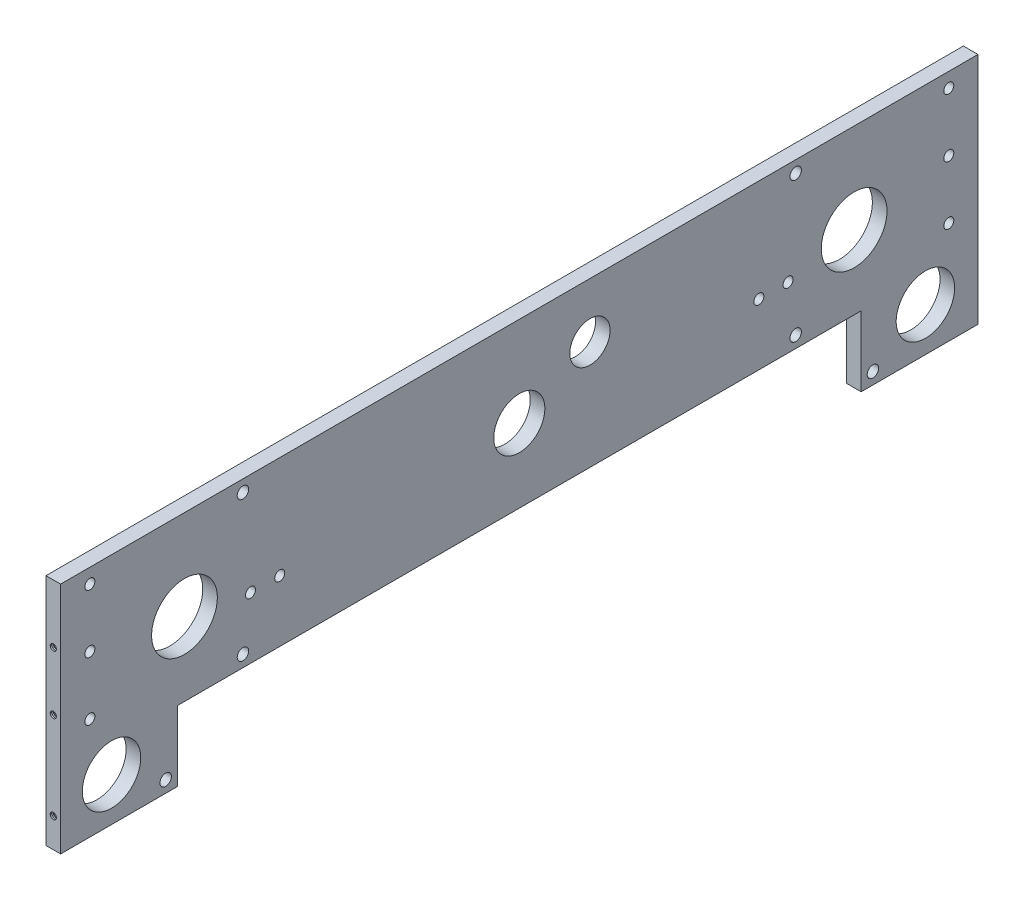
SolidWorks part; units mm, degrees
material "6061-T6 (SS)"
ref_plane "Front Plane" through (0, 0, 0) normal (0, 0, 1) x (1, 0, 0)
ref_plane "Top Plane" through (0, 0, 0) normal (0, 1, 0) x (1, 0, 0)
ref_plane "Right Plane" through (0, 0, 0) normal (1, 0, 0) x (0, 0, -1)
sketch "Sketch1" plane through (0, 0, 0) normal (1, 0, 0) x (0, 0, -1)
  line L1 (-199.39, 50.8) -> (199.39, 50.8)
  line L2 (-199.39, 50.8) -> (-199.39, -50.8)
  line L3 (-199.39, -50.8) -> (199.39, -50.8)
  line L4 (199.39, 50.8) -> (199.39, -50.8)
  line L5 (-199.39, 50.8) -> (199.39, -50.8) construction
  line L6 (-199.39, -50.8) -> (199.39, 50.8) construction
  point P0 (0, 0)
  dimension "D1" = 101.6
  dimension "D2" = 398.78
extrude "Boss-Extrude1" add sketch "Sketch1" along normal blind 6.35
sketch "Sketch2" plane through (6.35, 0, 0) normal (1, 0, 0) x (0, 0, -1)
  line L0 (-199.39, -50.8) -> (199.39, -50.8) construction
  line L1 (-145.5447, 11.6882) -> (0, 11.6882) construction
  line L2 (199.39, 50.8) -> (-199.39, 50.8) construction
  line L3 (0, 11.6882) -> (145.5447, 11.6882) construction
  line L4 (1.4287, 28.7746) -> (-143.1055, 40.86) construction
  line L5 (1.4287, -5.3983) -> (-143.1055, -17.4837) construction
  line L10 (0.9292, 22.8011) -> (-143.605, 34.8865) construction
  line L11 (-199.39, 50.8) -> (-199.39, -50.8) construction
  line L12 (-148.59, -50.8) -> (0, -50.8)
  line L13 (-148.59, -50.8) -> (-148.59, -20.32)
  line L14 (-148.59, -20.32) -> (148.59, -20.32)
  line L15 (0, -50.8) -> (0, -20.32) construction
  line L16 (199.39, -50.8) -> (199.39, 50.8) construction
  line L17 (-163.0212, -41.4951) -> (-132.9859, 3.2599) construction
  line L18 (0.9292, 0.5753) -> (-143.605, -11.5102) construction
  line L19 (-177.2583, -31.9405) -> (-199.39, -31.9405) construction
  line L20 (-177.2583, -31.9405) -> (-158.1418, -43.0925) construction
  line L21 (148.59, -50.8) -> (148.59, -20.32)
  line L22 (0, -50.8) -> (148.59, -50.8)
  line L23 (-120.1014, -15.5602) -> (-120.5589, -10.0878) construction
  line L24 (-120.5589, 40.5678) -> (-120.6912, 38.9858) construction
  circle A1 centre (-145.5447, 11.6882) radius 14.2875
  circle A2 centre (145.5447, 11.6882) radius 14.2875
  circle A3 centre (-145.5447, 11.6882) radius 29.2737 construction
  circle A4 centre (0, 11.6882) radius 30.48 construction
  circle A5 centre (145.5447, 11.6882) radius 29.2737 construction
  circle A11 centre (-177.2583, -31.9405) radius 12.7
  circle A12 centre (176.53, -31.9405) radius 12.7
  circle A13 centre (0, 11.6882) radius 11.1125
  circle A14 centre (-177.2583, -31.9405) radius 20.6375 construction
  circle A15 centre (-177.2583, -31.9405) radius 17.1461 construction
  circle A16 centre (-145.5447, 11.6882) radius 15.1248 construction
  circle A17 centre (0, 11.6882) radius 17.1461 construction
  circle A18 centre (34.3662, 11.6882) radius 8.7754 construction
  circle A19 centre (-153.715, -45.675) radius 5.125 construction
  circle A20 centre (-153.715, -45.675) radius 2.4892
  circle A21 centre (-120.1319, 45.675) radius 5.125 construction
  circle A22 centre (-120.1319, -15.195) radius 5.125 construction
  circle A23 centre (-120.1319, -15.195) radius 2.4892
  circle A24 centre (-120.1319, 45.675) radius 2.4892
  circle A25 centre (120.1319, 45.675) radius 2.4892
  circle A26 centre (120.1319, -15.195) radius 2.4892
  circle A27 centre (153.715, -45.675) radius 2.4892
  circle A28 centre (0, 11.6882) radius 29.21 construction
  circle A29 centre (30.7172, 26.9282) radius 5.08 construction
  circle A30 centre (30.7172, 26.9282) radius 8.75
  point P11 (0, 0)
  point P12 (0, -18.7918)
  point P14 (0, 42.1682)
  point P52 (-197.8958, -31.9405)
  point P56 (-159.8322, 11.6882)
  dimension "D1" = 28.575
  dimension "D5" = 58.5474
  dimension "D7" = 8.6318
  dimension "D14" = 25.4
  dimension "D15" = 53.9371
  dimension "D17" = 25.4
  dimension "D20" = 22.225
  dimension "D21" = 28.575
  dimension "D22" = 60.96
  dimension "D23" = 41.275
  dimension "D27" = 34.2921
  dimension "D28" = 30.2496
  dimension "D12" = 17.5508
  dimension "D13" = 10.25
  dimension "D29" = 4.9784
  dimension "D26" = 1.5875
  dimension "D30" = 4.9784
  dimension "D31" = 58.42
  dimension "D32" = 10.16
  dimension "D33" = 17.5001
  dimension "D3" = 39.5578
  dimension "D4" = 145.5447
  dimension "D6" = 0
  dimension "D8" = 1.5282
  dimension "D9" = 5.9944
  dimension "D10" = 5.9944
  dimension "D11" = 34.3662
  dimension "D16" = 1.4942
  dimension "D18" = 18.8595
  dimension "D19" = 22.86
  dimension "D24" = 30.48
  dimension "D25" = 50.8
  dimension "D34" = 15.24
extrude "Cut-Extrude1" cut sketch "Sketch2" against normal through all
sketch "Sketch3" plane through (6.35, 0, 0) normal (1, 0, 0) x (0, 0, -1)
  line L0 (-193.294, 19.05) -> (-193.294, -19.05) construction
  line L1 (-199.39, 50.8) -> (-199.39, -50.8) construction
  point P2 (-193.294, 0)
  point P3 (-199.39, 0)
  dimension "D1" = 38.1
  dimension "D2" = 6.096
sketch "Sketch27" plane through (0, 0, -199.39) normal (0, 0, -1) x (-1, 0, 0)
  line L0 (-6.35, 50.8) -> (0, 50.8) construction
  line L1 (-6.35, -50.8) -> (-6.35, 50.8) construction
  point P0 (-3.175, 25.4)
  point P1 (-3.175, 0)
  point P2 (-3.175, -38.1)
  dimension "D1" = 25.4
  dimension "D2" = 3.175
hole_wizard "#36 (0.1065) Diameter Hole2" positions "Sketch28" profile "Sketch29" hole size "#36" standard "ANSI Inch"
sketch "Sketch28" plane through (0, 0, -199.39) normal (0, 0, -1) x (-1, 0, 0)
  point P0 (-3.175, 25.4)
  point P3 (-3.175, 0)
  point P6 (-3.175, -38.1)
sketch "Sketch29" plane through (3.175, 25.4, -199.39) normal (1, 0, 0) x (0, 1, 0)
  line L0 (0, 0) -> (0, 9.7027)
  line L1 (0, 9.7027) -> (1.3525, 8.89)
  line L2 (1.3525, 8.89) -> (1.3525, 0)
  line L5 (1.3525, 0) -> (0, 0)
  line L10 (0, 9.7027) -> (-1.3526, 8.89) construction
  line L11 (0, -6.35) -> (0, 107.95) construction
  dimension "Hole Dia." = 2.7051
  dimension "Hole Depth" = 8.89
  dimension "Drill Angle" = 118
thread "Thread3" pitch 0.7937 method cut profile "Thread Profile3" start angle 0, offset 0, length 6.35, pitch 0.7937, diameter 2.7051
ref_plane "Plane3" through (4.5275, 25.4, -199.39) normal (0, -1, 0) x (1, 0, 0)
sketch "Thread Profile3" plane through (4.5275, 25.4, -199.39) normal (0, -1, 0) x (1, 0, 0)
  line L0 (0, 0) -> (0, 0.7937) construction
  line L1 (0, 0) -> (0.4296, 0.248)
  line L2 (0.4296, 0.248) -> (0.4296, 0.3473)
  line L3 (0.4296, 0.3473) -> (0, 0.5953)
  line L4 (0.4296, 0.2977) -> (0, 0.2977) construction
  line L11 (0, 0) -> (0, 0.5953)
  point P2 (0, 0)
  dimension "Pitch" = 0.7937
  dimension "Profile_Angle" = 60
  dimension "Profile_Land" = 0.0992
  dimension "Profile_Height" = 0.4296
thread "Thread4" pitch 0.7937 method cut profile "Thread Profile4" start angle 0, offset 0, length 6.35, pitch 0.7937, diameter 2.7051
ref_plane "Plane4" through (4.5275, 0, -199.39) normal (0, -1, 0) x (1, 0, 0)
sketch "Thread Profile4" plane through (4.5275, 0, -199.39) normal (0, -1, 0) x (1, 0, 0)
  line L0 (0, 0) -> (0, 0.7937) construction
  line L1 (0, 0) -> (0.4296, 0.248)
  line L2 (0.4296, 0.248) -> (0.4296, 0.3473)
  line L3 (0.4296, 0.3473) -> (0, 0.5953)
  line L4 (0.4296, 0.2977) -> (0, 0.2977) construction
  line L11 (0, 0) -> (0, 0.5953)
  point P2 (0, 0)
  dimension "Pitch" = 0.7937
  dimension "Profile_Angle" = 60
  dimension "Profile_Land" = 0.0992
  dimension "Profile_Height" = 0.4296
thread "Thread5" pitch 0.7937 method cut profile "Thread Profile5" start angle 0, offset 0, length 6.35, pitch 0.7937, diameter 2.7051
ref_plane "Plane5" through (4.5275, -38.1, -199.39) normal (0, -1, 0) x (1, 0, 0)
sketch "Thread Profile5" plane through (4.5275, -38.1, -199.39) normal (0, -1, 0) x (1, 0, 0)
  line L0 (0, 0) -> (0, 0.7937) construction
  line L1 (0, 0) -> (0.4296, 0.248)
  line L2 (0.4296, 0.248) -> (0.4296, 0.3473)
  line L3 (0.4296, 0.3473) -> (0, 0.5953)
  line L4 (0.4296, 0.2977) -> (0, 0.2977) construction
  line L11 (0, 0) -> (0, 0.5953)
  point P2 (0, 0)
  dimension "Pitch" = 0.7937
  dimension "Profile_Angle" = 60
  dimension "Profile_Land" = 0.0992
  dimension "Profile_Height" = 0.4296
sketch "Sketch36" plane through (0, 0, 199.39) normal (0, 0, 1) x (1, 0, 0)
  line L0 (6.35, 50.8) -> (6.35, -50.8) construction
  line L1 (6.35, 50.8) -> (0, 50.8) construction
  point P0 (3.175, 25.4)
  point P1 (3.175, -12.7)
  point P2 (3.175, -50.8)
  dimension "D1" = 25.4
  dimension "D2" = 3.175
  dimension "D3" = 38.1
  dimension "D4" = 38.1
hole_wizard "#36 (0.1065) Diameter Hole3" positions "Sketch37" profile "Sketch38" hole size "#36" standard "ANSI Inch"
sketch "Sketch37" plane through (0, 0, 199.39) normal (0, 0, 1) x (1, 0, 0)
  point P0 (3.175, 25.4)
  point P3 (3.175, 0)
  point P6 (3.175, -38.1)
sketch "Sketch38" plane through (3.175, 25.4, 199.39) normal (1, 0, 0) x (0, -1, 0)
  line L0 (0, 0) -> (0, 9.7027)
  line L1 (0, 9.7027) -> (1.3525, 8.89)
  line L2 (1.3525, 8.89) -> (1.3525, 0)
  line L5 (1.3525, 0) -> (0, 0)
  line L10 (0, 9.7027) -> (-1.3525, 8.89) construction
  line L11 (0, -6.35) -> (0, 107.95) construction
  dimension "Hole Dia." = 2.7051
  dimension "Hole Depth" = 8.89
  dimension "Drill Angle" = 118
thread "Thread6" pitch 0.7937 method cut profile "Thread Profile6" start angle 0, offset 0, length 6.35, pitch 0.7937, diameter 2.7051
ref_plane "Plane6" through (1.8225, 25.4, 199.39) normal (0, -1, 0) x (-1, 0, 0)
sketch "Thread Profile6" plane through (1.8225, 25.4, 199.39) normal (0, -1, 0) x (-1, 0, 0)
  line L0 (0, 0) -> (0, 0.7937) construction
  line L1 (0, 0) -> (0.4296, 0.248)
  line L2 (0.4296, 0.248) -> (0.4296, 0.3473)
  line L3 (0.4296, 0.3473) -> (0, 0.5953)
  line L4 (0.4296, 0.2977) -> (0, 0.2977) construction
  line L11 (0, 0) -> (0, 0.5953)
  point P2 (0, 0)
  dimension "Pitch" = 0.7937
  dimension "Profile_Angle" = 60
  dimension "Profile_Land" = 0.0992
  dimension "Profile_Height" = 0.4296
thread "Thread7" pitch 0.7937 method cut profile "Thread Profile7" start angle 0, offset 0, length 6.35, pitch 0.7937, diameter 2.7051
ref_plane "Plane7" through (1.8225, 0, 199.39) normal (0, -1, 0) x (-1, 0, 0)
sketch "Thread Profile7" plane through (1.8225, 0, 199.39) normal (0, -1, 0) x (-1, 0, 0)
  line L0 (0, 0) -> (0, 0.7937) construction
  line L1 (0, 0) -> (0.4296, 0.248)
  line L2 (0.4296, 0.248) -> (0.4296, 0.3473)
  line L3 (0.4296, 0.3473) -> (0, 0.5953)
  line L4 (0.4296, 0.2977) -> (0, 0.2977) construction
  line L11 (0, 0) -> (0, 0.5953)
  point P2 (0, 0)
  dimension "Pitch" = 0.7937
  dimension "Profile_Angle" = 60
  dimension "Profile_Land" = 0.0992
  dimension "Profile_Height" = 0.4296
thread "Thread8" pitch 0.7937 method cut profile "Thread Profile8" start angle 0, offset 0, length 6.35, pitch 0.7937, diameter 2.7051
ref_plane "Plane8" through (1.8225, -38.1, 199.39) normal (0, -1, 0) x (-1, 0, 0)
sketch "Thread Profile8" plane through (1.8225, -38.1, 199.39) normal (0, -1, 0) x (-1, 0, 0)
  line L0 (0, 0) -> (0, 0.7937) construction
  line L1 (0, 0) -> (0.4296, 0.248)
  line L2 (0.4296, 0.248) -> (0.4296, 0.3473)
  line L3 (0.4296, 0.3473) -> (0, 0.5953)
  line L4 (0.4296, 0.2977) -> (0, 0.2977) construction
  line L11 (0, 0) -> (0, 0.5953)
  point P2 (0, 0)
  dimension "Pitch" = 0.7937
  dimension "Profile_Angle" = 60
  dimension "Profile_Land" = 0.0992
  dimension "Profile_Height" = 0.4296
sketch "Sketch40" plane through (6.35, 0, 0) normal (1, 0, 0) x (0, 0, -1)
  line L4 (-199.39, -50.8) -> (-148.59, -50.8) construction
  line L5 (-199.39, 50.8) -> (-199.39, -50.8) construction
  line L6 (199.39, -50.8) -> (199.39, 50.8) construction
  line L7 (148.59, -50.8) -> (199.39, -50.8) construction
  point P2 (186.69, -6.35)
  point P3 (186.69, 19.05)
  point P4 (186.69, 44.45)
  point P7 (-186.69, -6.35)
  point P8 (-186.69, 19.05)
  point P9 (-186.69, 44.45)
  point P14 (0, 0)
  point P15 (0, 0)
  point P16 (0, 0)
  point P17 (0, 0)
  dimension "D2" = 12.7
  dimension "D3" = 25.4
  dimension "D4" = 25.4
  dimension "D5" = 44.45
  dimension "D6" = 25.4
  dimension "D7" = 25.4
  dimension "D8" = 44.45
  dimension "D10" = 12.7
hole_wizard "11/64 (0.17188) Diameter Hole1" positions "Sketch41" profile "Sketch43" hole size "11/64" standard "ANSI Inch" end condition through all
sketch "Sketch41" plane through (6.35, 0, 0) normal (1, 0, 0) x (0, 0, -1)
  point P0 (-186.69, 44.45)
  point P3 (-186.69, 19.05)
  point P6 (-186.69, -6.35)
  point P9 (186.69, -6.35)
  point P12 (186.69, 19.05)
  point P15 (186.69, 44.45)
sketch "Sketch43" plane through (6.35, 44.45, 186.69) normal (0, 1, 0) x (0, 0, -1)
  line L0 (0, 0) -> (0, 6.35)
  line L1 (0, 6.35) -> (2.1829, 6.35)
  line L2 (2.1829, 6.35) -> (2.1829, 0)
  line L5 (2.1829, 0) -> (0, 0)
  line L11 (0, -6.35) -> (0, 107.95) construction
  dimension "Thru Hole Dia." = 4.3658
  dimension "Thru Hole Depth" = 6.35
sketch "Sketch44" plane through (6.35, 0, 0) normal (1, 0, 0) x (0, 0, -1)
  line L0 (-199.39, 50.8) -> (-199.39, -50.8) construction
  line L1 (199.39, 50.8) -> (-199.39, 50.8) construction
  line L2 (199.39, -50.8) -> (199.39, 50.8) construction
  point P0 (-116.84, 6.35)
  point P1 (116.84, 6.35)
  point P8 (-104.14, 6.35)
  point P9 (104.14, 6.35)
  dimension "D1" = 82.55
  dimension "D2" = 44.45
  dimension "D3" = 82.55
  dimension "D6" = 12.7
  dimension "D7" = 12.7
hole_wizard "11/64 (0.17188) Diameter Hole2" positions "Sketch45" profile "Sketch46" hole size "11/64" standard "ANSI Inch" end condition through all
sketch "Sketch45" plane through (6.35, 0, 0) normal (1, 0, 0) x (0, 0, -1)
  point P0 (-116.84, 6.35)
  point P3 (116.84, 6.35)
  point P7 (-104.14, 6.35)
  point P10 (104.14, 6.35)
sketch "Sketch46" plane through (6.35, 6.35, 116.84) normal (0, 1, 0) x (0, 0, -1)
  line L0 (0, 0) -> (0, 6.35)
  line L1 (0, 6.35) -> (2.1829, 6.35)
  line L2 (2.1829, 6.35) -> (2.1829, 0)
  line L5 (2.1829, 0) -> (0, 0)
  line L11 (0, -6.35) -> (0, 107.95) construction
  dimension "Thru Hole Dia." = 4.3658
  dimension "Thru Hole Depth" = 6.35
